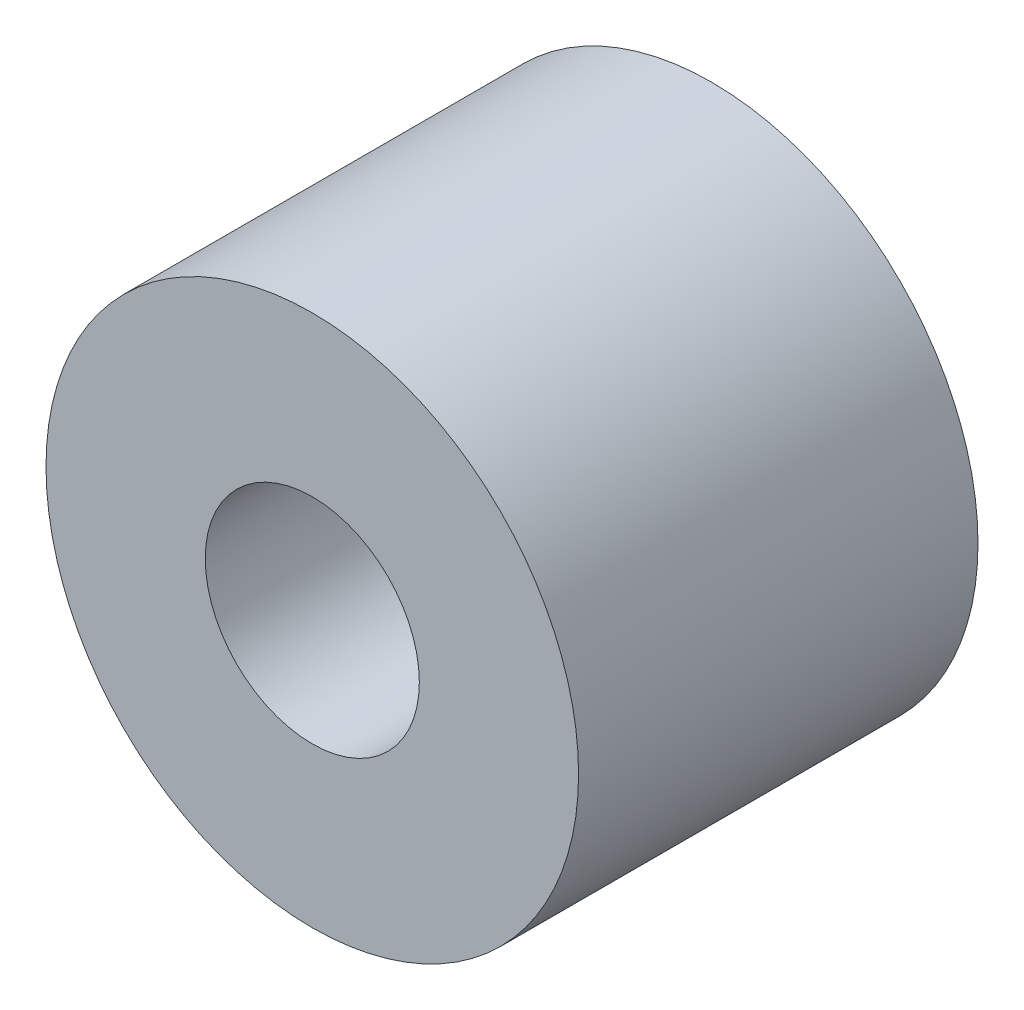
SolidWorks part; units mm, degrees
ref_plane "Front Plane" through (0, 0, 0) normal (0, 0, 1) x (1, 0, 0)
ref_plane "Top Plane" through (0, 0, 0) normal (0, 1, 0) x (1, 0, 0)
ref_plane "Right Plane" through (0, 0, 0) normal (1, 0, 0) x (0, 0, -1)
sketch "Sketch1" plane through (0, 0, 0) normal (0, 0, 1) x (1, 0, 0)
  circle A0 centre (0, 0) radius 6.35
  dimension "D1" = 12.7
extrude "Boss-Extrude1" add sketch "Sketch1" along normal mid plane 9.525
sketch "Sketch2" plane through (0, 0, 4.7625) normal (0, 0, 1) x (1, 0, 0)
  point P0 (0, 0)
hole_wizard "Tap Drill for 1/4-20 Tap1" positions "Sketch2" profile "Sketch3" hole size "1/4-20" standard "ANSI Inch" end condition through all
sketch "Sketch3" plane through (0, 0, 4.7625) normal (1, 0, 0) x (0, -1, 0)
  line L0 (0, 0) -> (0, 9.525)
  line L1 (0, 9.525) -> (2.5527, 9.525)
  line L2 (2.5527, 9.525) -> (2.5527, 0)
  line L5 (2.5527, 0) -> (0, 0)
  line L11 (0, -6.35) -> (0, 107.95) construction
  dimension "Thru Hole Dia." = 5.1054
  dimension "Thru Hole Depth" = 9.525
cosmetic thread "Cosmetic Thread1"
equation "\"AIRFRAME_OD\"= 3.091in"
equation "\"AIRFRAME_ID\"= 3.00in"
equation "\"FLAT_T\"= 0.125in"
equation "\"NOSE_EXP_L\"= 3.5in"
equation "\"NOSE_SHOULDER_L\"= 5in"
equation "\"MAIN_L\"= 30in"
equation "\"RECO_COUP_L\"= 6in"
equation "\"RECO_SWITCH_L\"= 1.5in"
equation "\"DROGUE_L\"= 14in"
equation "\"ATS_FORE_COUP_L\"= 4in"
equation "\"ATS_AFT_COUP_L\"= 2.5in"
equation "\"LOWER_L\"= 16in"
equation "\"FIN_N\"= 4"
equation "\"CR_AFT_X\"= 0.5in"
equation "\"CR_FORE_X\"= 6in"
